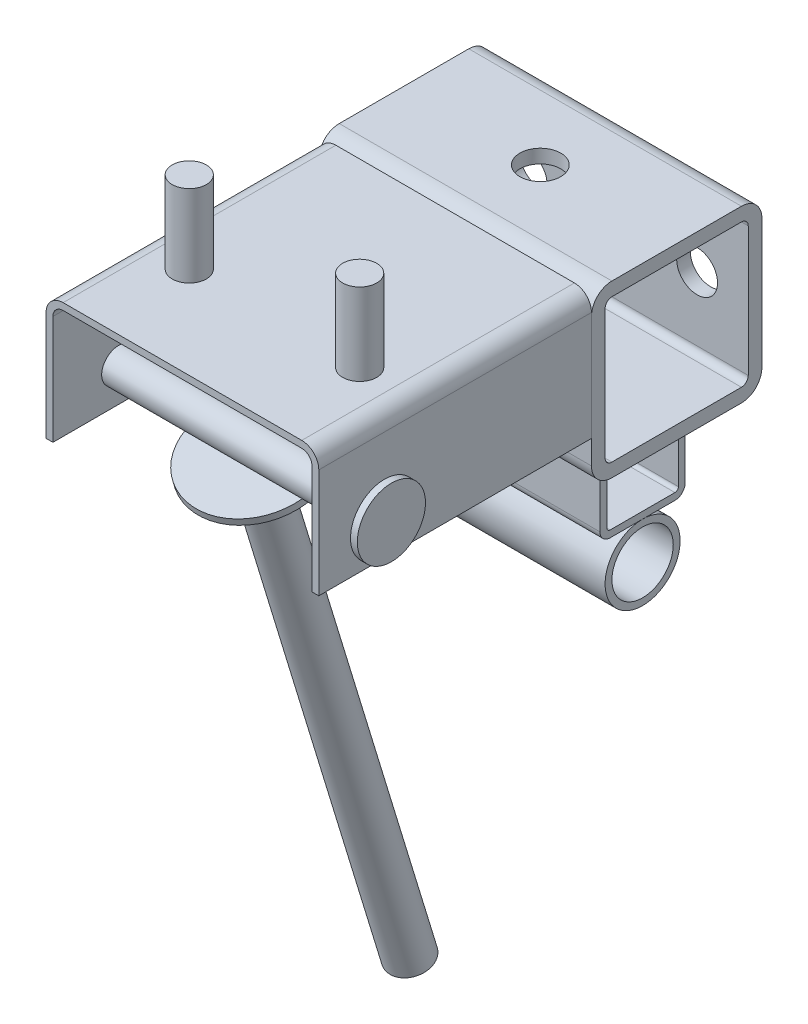
SolidWorks part; units mm, degrees
note: The reader was unsure of these and kept them because the rebuilt part matched: shared geometry of "Эскиз7<3>".
ref_plane "Спереди" through (0, 0, 0) normal (0, 0, 1) x (1, 0, 0)
ref_plane "Сверху" through (0, 0, 0) normal (0, 1, 0) x (1, 0, 0)
ref_plane "Справа" through (0, 0, 0) normal (1, 0, 0) x (0, 0, -1)
sketch "Эскиз1" plane through (0, 0, 0) normal (0, 0, 1) x (1, 0, 0)
  line L0 (-40, 0) -> (40, 0)
  point P4 (0, 0)
  dimension "D1" = 80
other "Труба bxbxs гост8639-82 50 X 50 X 4(1)" corner treatment miter
ref_plane "Плоскость1" through (-40, 0, 0) normal (1, 0, 0) x (0, 1, 0)
sketch "Sketch1" plane through (-40, 0, 0) normal (1, 0, 0) x (0, 1, 0)
  line L0 (-19, -21) -> (19, -21)
  line L1 (-21, -19) -> (-21, 19)
  line L2 (19, 21) -> (-19, 21)
  line L3 (21, 19) -> (21, -19)
  line L4 (-19, -25) -> (19, -25)
  line L5 (-25, -19) -> (-25, 19)
  line L6 (19, 25) -> (-19, 25)
  line L7 (25, 19) -> (25, -19)
  arc A0 (25, 19) -> (19, 25) centre (19, 19) ccw
  arc A1 (19, -25) -> (25, -19) centre (19, -19) ccw
  arc A2 (-25, -19) -> (-19, -25) centre (-19, -19) ccw
  arc A3 (-19, 25) -> (-25, 19) centre (-19, 19) ccw
  arc A4 (-19, 21) -> (-21, 19) centre (-19, 19) ccw
  arc A5 (21, 19) -> (19, 21) centre (19, 19) ccw
  arc A6 (19, -21) -> (21, -19) centre (19, -19) ccw
  arc A7 (-21, -19) -> (-19, -21) centre (-19, -19) ccw
  point P0 (-25, 0)
  point P1 (25, 0)
  point P2 (0, 25)
  point P3 (0, -25)
  point P4 (0, 0)
  point P5 (-25, -25)
  point P6 (25, -25)
  point P7 (25, 25)
  point P8 (-25, 25)
  point P33 (0, 0)
  dimension "D1" = 6
  dimension "Thickness" = 4
  dimension "V_leg" = 50
sketch "Эскиз3" plane through (0, 0, 25) normal (0, 0, 1) x (1, 0, 0)
  line L0 (-40, -12) -> (-40, 20)
  line L1 (-40, 19) -> (-40, -19) construction
  line L2 (-35, 25) -> (35, 25)
  line L3 (40, 20) -> (40, -12)
  line L4 (40, 19) -> (40, -19) construction
  line L5 (-38, -12) -> (-38, 20)
  line L6 (-35, 23) -> (35, 23)
  line L7 (38, 20) -> (38, -12)
  line L8 (-40, -12) -> (-38, -12)
  line L9 (38, -12) -> (40, -12)
  arc A0 (-40, 20) -> (-35, 25) centre (-35, 20) cw
  arc A1 (35, 25) -> (40, 20) centre (35, 20) cw
  arc A2 (-38, 20) -> (-35, 23) centre (-35, 20) cw
  arc A3 (35, 23) -> (38, 20) centre (35, 20) cw
  point P13 (-40, 25)
  point P16 (40, 25)
  dimension "D2" = 5
  dimension "D1" = 37
  dimension "D3" = 2
extrude "Бобышка-Вытянуть1" add sketch "Эскиз3" along normal blind 80 separate body
ref_plane "Плоскость2" through (0, -37.5, 0) normal (0, -1, 0) x (-1, 0, 0)
sketch "Эскиз4" plane through (0, -37.5, 0) normal (0, -1, 0) x (-1, 0, 0)
  line L0 (-30, 0) -> (30, 0)
  line L1 (40, 0) -> (-40, 0) construction
  point P6 (0, 0)
  dimension "D1" = 60
other "Труба bxbxs гост8639-82 25 X 25 X 2(1)" corner treatment miter
ref_plane "Плоскость3" through (30, -37.5, 0) normal (-1, 0, 0) x (0, 0, -1)
sketch "Sketch11" plane through (30, -37.5, 0) normal (-1, 0, 0) x (0, 0, -1)
  line L0 (-9.5, -10.5) -> (9.5, -10.5)
  line L1 (-10.5, -9.5) -> (-10.5, 9.5)
  line L2 (9.5, 10.5) -> (-9.5, 10.5)
  line L3 (10.5, 9.5) -> (10.5, -9.5)
  line L4 (-9.5, -12.5) -> (9.5, -12.5)
  line L5 (-12.5, -9.5) -> (-12.5, 9.5)
  line L6 (9.5, 12.5) -> (-9.5, 12.5)
  line L7 (12.5, 9.5) -> (12.5, -9.5)
  arc A0 (12.5, 9.5) -> (9.5, 12.5) centre (9.5, 9.5) ccw
  arc A1 (9.5, -12.5) -> (12.5, -9.5) centre (9.5, -9.5) ccw
  arc A2 (-12.5, -9.5) -> (-9.5, -12.5) centre (-9.5, -9.5) ccw
  arc A3 (-9.5, 12.5) -> (-12.5, 9.5) centre (-9.5, 9.5) ccw
  arc A4 (-9.5, 10.5) -> (-10.5, 9.5) centre (-9.5, 9.5) ccw
  arc A5 (10.5, 9.5) -> (9.5, 10.5) centre (9.5, 9.5) ccw
  arc A6 (9.5, -10.5) -> (10.5, -9.5) centre (9.5, -9.5) ccw
  arc A7 (-10.5, -9.5) -> (-9.5, -10.5) centre (-9.5, -9.5) ccw
  point P0 (-12.5, 0)
  point P1 (12.5, 0)
  point P2 (0, 12.5)
  point P3 (0, -12.5)
  point P4 (0, 0)
  point P5 (-12.5, -12.5)
  point P6 (12.5, -12.5)
  point P7 (12.5, 12.5)
  point P8 (-12.5, 12.5)
  point P33 (0, 0)
  dimension "D1" = 3
  dimension "Thickness" = 2
  dimension "V_leg" = 25
sketch "Эскиз6" plane through (30, 0, 0) normal (1, 0, 0) x (0, 0, -1)
  line L0 (9.5, -50) -> (-9.5, -50) construction
  circle A0 centre (0, -61) radius 11
  circle A1 centre (0, -61) radius 9
  dimension "D1" = 22
  dimension "D2" = 18
extrude "Бобышка-Вытянуть2" add sketch "Эскиз6" against normal blind 60 separate body
sketch "Эскиз7" plane through (40, 0, 0) normal (1, 0, 0) x (0, 0, -1)
  line L0 (-105, -12) -> (-25, -12) construction
  line L1 (-105, -12) -> (-105, 20) construction
  circle A0 centre (-85.7, -2) radius 5
  circle A1 centre (-85.7, -2) radius 10
  dimension "D1" = 10
  dimension "D2" = 20
  dimension "D3" = 9.3
extrude "Бобышка-Вытянуть3" add sketch "Эскиз7" along normal blind 2 separate body contours A1 A0 | A0
mirror "Зеркальное отражение1" about plane through (0, 0, 0) normal (1, 0, 0) of bodies 107
extrude "Бобышка-Вытянуть4" add sketch "Эскиз7<3>" against normal blind 82 separate body contours A0
sketch "Эскиз7<3>" plane through (40, 0, 0) normal (1, 0, 0) x (0, 0, -1) same geometry as "Эскиз7"
ref_plane "Плоскость4" through (0, 17.3509, 5.3047) normal (0, -0.9563, -0.2924) x (1, 0, 0)
sketch "Эскиз8" plane through (0, 17.3509, 5.3047) normal (0, -0.9563, -0.2924) x (1, 0, 0)
  line L1 (42, 82.5401) -> (-48.5224, 82.5401) construction
  line L2 (42, 72.5401) -> (42, 92.5401) construction
  circle A0 centre (0, 82.5401) radius 17.5
  dimension "D1" = 35
extrude "Бобышка-Вытянуть5" add sketch "Эскиз8" along normal blind 2 separate body
sketch "Эскиз9" plane through (0, 25, 0) normal (0, 1, 0) x (1, 0, 0)
  line L0 (0, -105) -> (0, -66.9515) construction
  line L1 (35, -105) -> (-35, -105) construction
  circle A0 centre (-25, -78) radius 5
  circle A1 centre (25, -78) radius 5
  dimension "D2" = 10
  dimension "D1" = 50
  dimension "D3" = 22
extrude "Бобышка-Вытянуть6" add sketch "Эскиз9" along normal blind 24 separate body
sketch "Эскиз10" plane through (0, 25, 0) normal (0, 1, 0) x (1, 0, 0)
  circle A0 centre (0, 0) radius 6
  dimension "D1" = 12
extrude "Вырез-Вытянуть1" cut sketch "Эскиз10" against normal up to next (4 mm away)
sketch "Эскиз11" plane through (0, 0, -25) normal (0, 0, -1) x (-1, 0, 0)
  line L0 (0, 0) -> (0, 49.3176) construction
  circle A0 centre (25, 0) radius 6
  circle A1 centre (-25, 0) radius 6
  dimension "D1" = 12
  dimension "D2" = 50
extrude "Вырез-Вытянуть2" cut sketch "Эскиз11" against normal up to next (4 mm away)
sketch "Эскиз12" plane through (0, 15.4382, 4.7199) normal (0, -0.9563, -0.2924) x (1, 0, 0)
  circle A0 centre (0, 82.5401) radius 6
  dimension "D1" = 12
extrude "Бобышка-Вытянуть7" add sketch "Эскиз12" along normal blind 155 separate body
